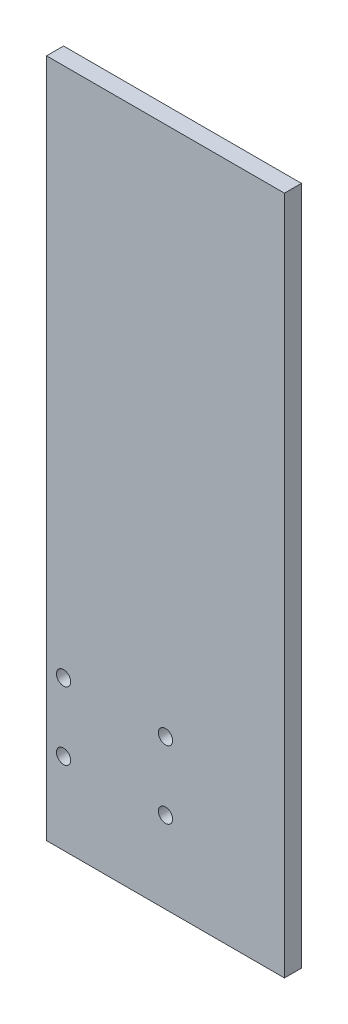
SolidWorks part; units mm, degrees
ref_plane "정면" through (0, 0, 0) normal (0, 0, 1) x (1, 0, 0)
ref_plane "윗면" through (0, 0, 0) normal (0, 1, 0) x (1, 0, 0)
ref_plane "우측면" through (0, 0, 0) normal (1, 0, 0) x (0, 0, -1)
sketch "스케치1" plane through (0, 0, 0) normal (0, 0, 1) x (1, 0, 0)
  line L1 (-50, 100) -> (50, 100)
  line L2 (-50, 100) -> (-50, -100)
  line L3 (-50, -100) -> (50, -100)
  line L4 (50, 100) -> (50, -100)
  line L5 (-50, 100) -> (50, -100) construction
  line L6 (-50, -100) -> (50, 100) construction
  point P0 (0, 0)
  dimension "D1" = 100
  dimension "D2" = 200
extrude "보스-돌출1" add sketch "스케치1" along normal blind 5
sketch "스케치3" plane through (0, 0, 0) normal (0, 0, -1) x (-1, 0, 0)
  text T0 "front"
extrude "컷-돌출2" cut sketch "스케치3" against normal blind 0.001
ref_plane "평면1" through (0, 0, -5) normal (0, 0, -1) x (-1, 0, 0)
hole_wizard "M4x0.7 Helicoil용 탭 구멍1" positions "스케치10" profile "스케치11" tap size "M4x0.7" standard "Helicoil® Metric" end condition through all
sketch "스케치10" plane through (0, 0, -5) normal (0, 0, -1) x (-1, 0, 0)
  line L0 (50, -100) -> (-50, -100) construction
  line L1 (-50, -100) -> (-50, 100) construction
  line L2 (50, 100) -> (50, -100) construction
  point P0 (5, -76)
  point P2 (35, -76)
  point P4 (5, -56)
  point P6 (35, -56)
  dimension "D1" = 24
  dimension "D2" = 24
  dimension "D3" = 55
  dimension "D4" = 15
  dimension "D5" = 15
  dimension "D6" = 55
  dimension "D7" = 20
  dimension "D8" = 20
sketch "스케치11" plane through (-5, -76, -5) normal (1, 0, 0) x (0, 1, 0)
  line L0 (0, 0) -> (0, 10)
  line L1 (0, 10) -> (2.1, 10)
  line L2 (2.1, 10) -> (2.1, 0)
  line L5 (2.1, 0) -> (0, 0)
  line L11 (0, -6.35) -> (0, 107.95) construction
  dimension "관통 탭 드릴 지름" = 4.2
  dimension "관통 탭 드릴 깊이" = 10
cosmetic thread "구멍 나사산1" parameters "D1"=4.7, "D2"=5.007
cosmetic thread "구멍 나사산2" parameters "D1"=4.7, "D2"=5.007
cosmetic thread "구멍 나사산3" parameters "D1"=4.7, "D2"=5.007
cosmetic thread "구멍 나사산4" parameters "D1"=4.7, "D2"=5.007
sketch "스케치13" plane through (0, 0, 5) normal (0, 0, 1) x (1, 0, 0)
  line L0 (-50, -100) -> (50, -100) construction
  line L1 (50, 100) -> (40, 100)
  line L2 (50, 100) -> (50, -100)
  line L3 (50, -100) -> (40, -100)
  line L4 (40, 100) -> (40, -100)
  line L5 (0, -2.75) -> (0, 2.75) construction
  line L6 (-40, 100) -> (-40, -100)
  line L7 (-50, -100) -> (-40, -100)
  line L8 (-50, 100) -> (-50, -100)
  line L9 (-50, 100) -> (-40, 100)
  dimension "D1" = 10
extrude "컷-돌출4" cut sketch "스케치13" against normal blind 10
sketch "스케치14" plane through (0, 0, 5) normal (0, 0, 1) x (1, 0, 0)
  line L0 (-40, -100) -> (40, -100) construction
  line L1 (40, 100) -> (30, 100)
  line L2 (40, 100) -> (40, -100)
  line L3 (40, -100) -> (30, -100)
  line L4 (30, 100) -> (30, -100)
  dimension "D1" = 10
extrude "컷-돌출5" cut sketch "스케치14" against normal blind 10
